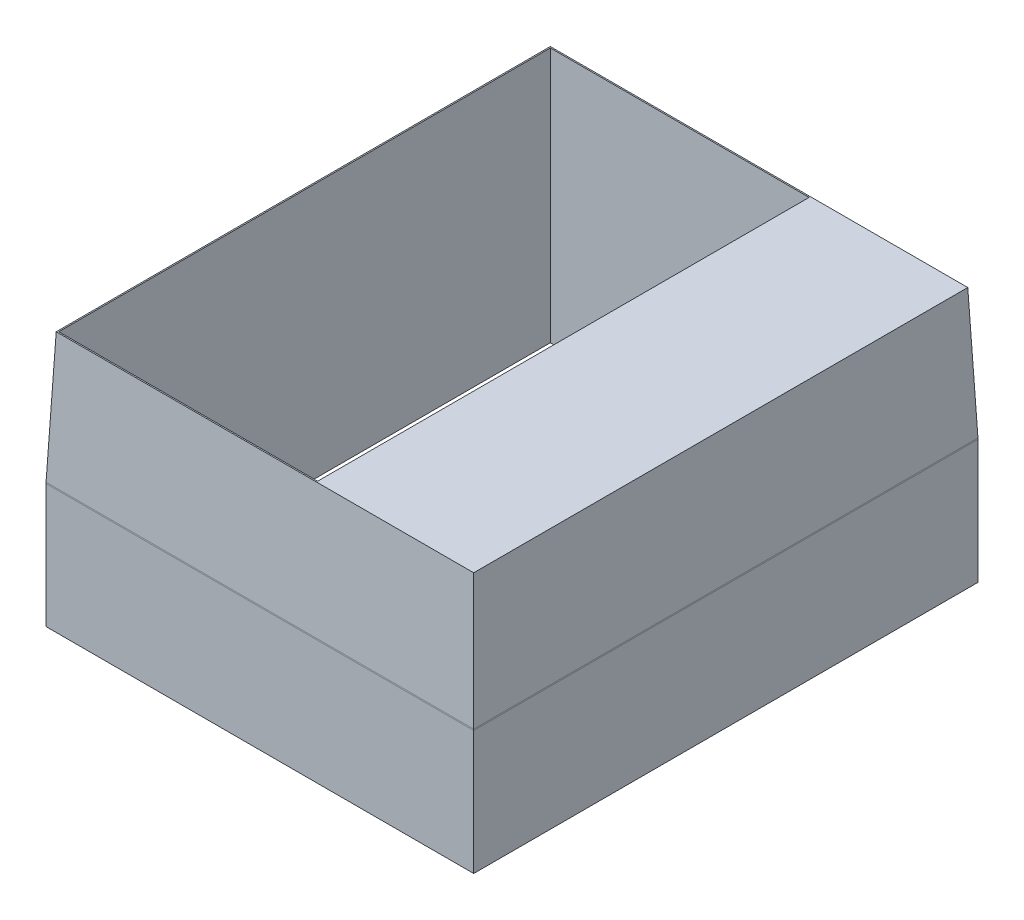
SolidWorks part; units mm, degrees
material "Silikongummi"
ref_plane "Ebene vorne" through (0, 0, 0) normal (0, 0, 1) x (1, 0, 0)
ref_plane "Ebene oben" through (0, 0, 0) normal (0, 1, 0) x (1, 0, 0)
ref_plane "Ebene rechts" through (0, 0, 0) normal (1, 0, 0) x (0, 0, -1)
sketch "Skizze1" plane through (0, 0, 0) normal (0, 1, 0) x (1, 0, 0)
  line L1 (0, 0) -> (40.55, 0)
  line L2 (0, 0) -> (0, 77)
  line L3 (0, 77) -> (40.55, 77)
  line L4 (40.55, 0) -> (40.55, 77)
  line L5 (-1, 78) -> (66, 78)
  line L6 (-1, 78) -> (-1, -1)
  line L7 (-1, -1) -> (66, -1)
  line L8 (66, 78) -> (66, -1)
  dimension "D1" = 77
  dimension "D2" = 40.55
  dimension "D3" = 1
  dimension "D4" = 25.45
  dimension "D5" = 1
  dimension "D6" = 1
extrude "Aufsatz-Linear austragen2" add sketch "Skizze1" along normal blind 40
chamfer "Fase1" distance 20.5 distance2 0.8 4 edges at (32.5, 40, -78) (66, 40, -38.5) (32.5, 40, 1) (-1, 40, -38.5) first distance on face at (32.5, 20, -78) first distance on face at (66, 20, -38.5) first distance on face at (32.5, 20, 1) first distance on face at (-1, 20, -38.5)
fillet "Verrundung2" radius 5 4 edges at (66, 19.5, -38.5) (32.5, 19.5, -78) (-1, 19.5, -38.5) (32.5, 19.5, 1)
